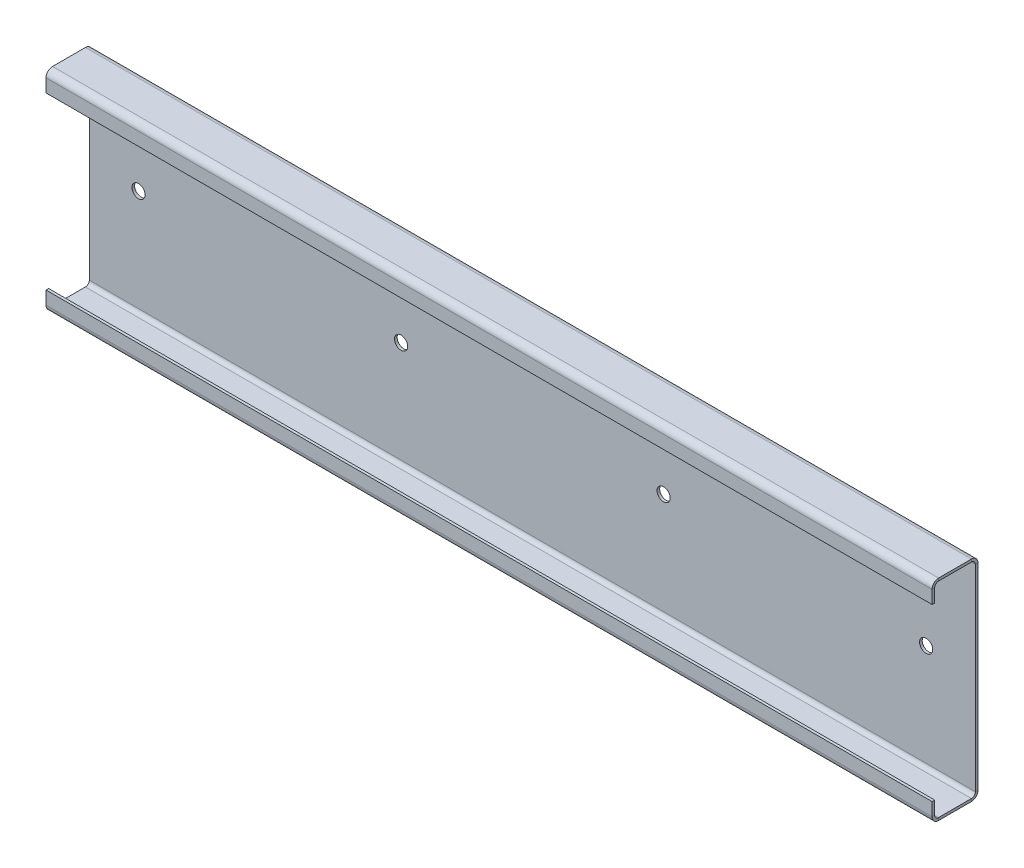
SolidWorks part; units mm, degrees
note: The reader was unsure of these and kept them because the rebuilt part matched: thickness of "Base-Flange1", "Edge-Flange1", "Edge-Flange2", "Sheet-Metal1", "Sheet-Metal2", "Sheet-Metal3", "Sheet-Metal5", "Sheet-Metal6"; flange length of "Edge-Flange1", "Edge-Flange2".
material "Galvanized Steel"
ref_plane "Front Plane" through (0, 0, 0) normal (0, 0, 1) x (1, 0, 0)
ref_plane "Top Plane" through (0, 0, 0) normal (0, 1, 0) x (1, 0, 0)
ref_plane "Right Plane" through (0, 0, 0) normal (1, 0, 0) x (0, 0, -1)
sketch "Sketch1" plane through (0, 0, 0) normal (0, 0, 1) x (1, 0, 0)
  line L1 (-337.5, -80) -> (337.5, -80)
  line L2 (-337.5, -80) -> (-337.5, 80)
  line L3 (-337.5, 80) -> (337.5, 80)
  line L4 (337.5, -80) -> (337.5, 80)
  line L5 (-337.5, -80) -> (337.5, 80) construction
  line L6 (-337.5, 80) -> (337.5, -80) construction
  point P0 (0, 0)
  dimension "D1" = 675
  dimension "D2" = 160
base flange "Base-Flange1" sketch "Sketch1" thickness 2 reverse thickness direction no parameters "D1"=3
edge flange "Edge-Flange1" sketch "Sketch10" flange profiles "Sketch10", "Sketch11" flange angle 90 flange length 35 flange position material inside bend radius 3 thickness 2 relief rectangular parameters "D6"=10, "D8"=1
sketch "Sketch10" plane through (0, 80, 0) normal (0, 1, 0) x (-1, 0, 0)
  line L0 (-337.5, 0) -> (337.5, 0) construction
  line L1 (-337.5, 0) -> (337.5, 0)
  line L2 (-337.5, 0) -> (-337.5, 33)
  line L3 (-337.5, 33) -> (337.5, 33)
  line L4 (337.5, 33) -> (337.5, 0)
sketch "Sketch11" plane through (0, -80, 0) normal (0, -1, 0) x (1, 0, 0)
  line L0 (-337.5, 0) -> (337.5, 0) construction
  line L1 (-337.5, 0) -> (337.5, 0)
  line L2 (-337.5, 0) -> (-337.5, 33)
  line L3 (-337.5, 33) -> (337.5, 33)
  line L4 (337.5, 33) -> (337.5, 0)
bend "EdgeBend1" bend radius 3 bend angle 90 parameters "D5"=1
bend "EdgeBend2" bend radius 3 bend angle 90 parameters "D5"=2
edge flange "Edge-Flange2" sketch "Sketch16" flange profiles "Sketch16", "Sketch17" flange angle 90 flange length 15 flange position material inside bend radius 3 thickness 2 relief rectangular parameters "D6"=10, "D8"=1
sketch "Sketch16" plane through (0, -78, 33) normal (0, 0, 1) x (1, 0, 0)
  line L0 (337.5, 0) -> (-337.5, 0) construction
  line L1 (337.5, 0) -> (-337.5, 0)
  line L2 (-337.5, 0) -> (-337.5, 13)
  line L3 (-337.5, 13) -> (337.5, 13)
  line L4 (337.5, 13) -> (337.5, 0)
sketch "Sketch17" plane through (0, 78, 33) normal (0, 0, 1) x (-1, 0, 0)
  line L0 (337.5, 0) -> (-337.5, 0) construction
  line L1 (337.5, 0) -> (-337.5, 0)
  line L2 (-337.5, 0) -> (-337.5, 13)
  line L3 (-337.5, 13) -> (337.5, 13)
  line L4 (337.5, 13) -> (337.5, 0)
bend "EdgeBend3" bend radius 3 bend angle 90 parameters "D5"=3
bend "EdgeBend4" bend radius 3 bend angle 90 parameters "D5"=4
sketch "Sketch18" plane through (0, 0, -2) normal (0, 0, -1) x (-1, 0, 0)
  line L0 (337.5, 80) -> (-337.5, 80) construction
  line L1 (-337.5, -75) -> (-337.5, 75) construction
  circle A0 centre (-300, 2.49) radius 5
  dimension "D1" = 10
  dimension "D2" = 77.51
  dimension "D3" = 37.5
extrude "Cut-Extrude1" cut sketch "Sketch18" against normal blind 10 normal cut yes
pattern_linear "LPattern1" count 4 spacing 200 along (-1, 0, 0) of "Cut-Extrude1"
sketch "Bend-Lines1" [suppressed] plane through (0, 0, 0) normal (0, 1, 0) x (1, 0, 0)
sketch "Bounding-Box1" [suppressed] plane through (0, 0, 0) normal (0, 1, 0) x (1, 0, 0)
sheet metal parameters "Sheet-Metal1" thickness 2 parameters "D1"=3
flat pattern "Flat-Pattern1" [suppressed]
sketch "Bend-Lines2" plane through (0, 0, 0) normal (0, 1, 0) x (1, 0, 0)
sketch3d "Bounding-Box2" [suppressed]
  line L0 (710, -80, 0) -> (-710, -80, 0) construction
  line L1 (710, 80, 0) -> (-710, 80, 0) construction
  line L2 (710, -80, 0) -> (710, 80, 0) construction
  line L3 (-710, -80, 0) -> (-710, 80, 0) construction
sheet metal parameters "Sheet-Metal2" thickness 2 parameters "D1"=3, "D7"=1.5
flat pattern "Flat-Pattern1"
sketch "Bend-Lines2" plane through (0, 0, 0) normal (0, 0, 1) x (1, 0, 0)
  line L0 (-710, -78.4452) -> (710, -78.4452) construction
  line L1 (710, 78.4452) -> (-710, 78.4452) construction
  line L2 (-710, -78.4452) -> (710, -78.4452) construction
  line L3 (710, 78.4452) -> (-710, 78.4452) construction
sketch3d "Bounding-Box2" [suppressed]
  line L0 (-710, -111.8905, 0) -> (710, -111.8905, 0) construction
  line L1 (-710, 111.8905, 0) -> (710, 111.8905, 0) construction
  line L2 (-710, -111.8905, 0) -> (-710, 111.8905, 0) construction
  line L3 (710, -111.8905, 0) -> (710, 111.8905, 0) construction
bend of the flat pattern "Flatten-<EdgeBend1>1"
bend of the flat pattern "Flatten-<EdgeBend2>1"
sheet metal parameters "Sheet-Metal3" thickness 2 parameters "D1"=3, "D7"=1.5
flat pattern "Flat-Pattern1"
sketch "Bend-Lines2" plane through (0, 0, 0) normal (0, 0, 1) x (1, 0, 0)
  line L0 (-337.5, -78.1416) -> (337.5, -78.1416) construction
  line L1 (337.5, 78.1416) -> (-337.5, 78.1416) construction
  line L2 (-337.5, -78.1416) -> (337.5, -78.1416) construction
  line L3 (337.5, 78.1416) -> (-337.5, 78.1416) construction
  line L4 (337.5, 109.4248) -> (-337.5, 109.4248) construction
  line L5 (-337.5, -109.4248) -> (337.5, -109.4248) construction
  line L6 (337.5, 109.4248) -> (-337.5, 109.4248) construction
  line L7 (-337.5, -109.4248) -> (337.5, -109.4248) construction
sketch3d "Bounding-Box2" [suppressed]
  line L0 (-337.5, -122.5664, 0) -> (337.5, -122.5664, 0) construction
  line L1 (-337.5, 122.5664, 0) -> (337.5, 122.5664, 0) construction
  line L2 (-337.5, -122.5664, 0) -> (-337.5, 122.5664, 0) construction
  line L3 (337.5, -122.5664, 0) -> (337.5, 122.5664, 0) construction
bend of the flat pattern "Flatten-<EdgeBend1>1"
bend of the flat pattern "Flatten-<EdgeBend2>1"
bend of the flat pattern "Flatten-<EdgeBend3>1"
bend of the flat pattern "Flatten-<EdgeBend4>1"
sheet metal parameters "Sheet-Metal5" thickness 2 parameters "D1"=3, "D7"=1.5
flat pattern "Flat-Pattern1"
sketch "Bend-Lines2" plane through (0, 0, 0) normal (0, 0, 1) x (1, 0, 0)
  line L0 (-337.5, -78.1416) -> (337.5, -78.1416) construction
  line L1 (337.5, 78.1416) -> (-337.5, 78.1416) construction
  line L2 (-337.5, -78.1416) -> (337.5, -78.1416) construction
  line L3 (337.5, 78.1416) -> (-337.5, 78.1416) construction
  line L4 (337.5, 109.4248) -> (-337.5, 109.4248) construction
  line L5 (-337.5, -109.4248) -> (337.5, -109.4248) construction
  line L6 (337.5, 109.4248) -> (-337.5, 109.4248) construction
  line L7 (-337.5, -109.4248) -> (337.5, -109.4248) construction
sketch3d "Bounding-Box2" [suppressed]
  line L0 (-337.5, -122.5664, 0) -> (337.5, -122.5664, 0) construction
  line L1 (-337.5, 122.5664, 0) -> (337.5, 122.5664, 0) construction
  line L2 (-337.5, -122.5664, 0) -> (-337.5, 122.5664, 0) construction
  line L3 (337.5, -122.5664, 0) -> (337.5, 122.5664, 0) construction
bend of the flat pattern "Flatten-<EdgeBend1>1"
bend of the flat pattern "Flatten-<EdgeBend2>1"
bend of the flat pattern "Flatten-<EdgeBend3>1"
bend of the flat pattern "Flatten-<EdgeBend4>1"
sheet metal parameters "Sheet-Metal6" thickness 2 parameters "D1"=3, "D7"=1.5
flat pattern "Flat-Pattern1"
sketch "Bend-Lines2" plane through (0, 0, 0) normal (0, 0, 1) x (1, 0, 0)
  line L0 (-337.5, -78.1416) -> (337.5, -78.1416) construction
  line L1 (337.5, 78.1416) -> (-337.5, 78.1416) construction
  line L2 (-337.5, -78.1416) -> (337.5, -78.1416) construction
  line L3 (337.5, 78.1416) -> (-337.5, 78.1416) construction
  line L4 (337.5, 109.4248) -> (-337.5, 109.4248) construction
  line L5 (-337.5, -109.4248) -> (337.5, -109.4248) construction
  line L6 (337.5, 109.4248) -> (-337.5, 109.4248) construction
  line L7 (-337.5, -109.4248) -> (337.5, -109.4248) construction
sketch3d "Bounding-Box2" [suppressed]
  line L0 (-337.5, -122.5664, 0) -> (337.5, -122.5664, 0) construction
  line L1 (-337.5, 122.5664, 0) -> (337.5, 122.5664, 0) construction
  line L2 (-337.5, -122.5664, 0) -> (-337.5, 122.5664, 0) construction
  line L3 (337.5, -122.5664, 0) -> (337.5, 122.5664, 0) construction
bend of the flat pattern "Flatten-<EdgeBend1>1"
bend of the flat pattern "Flatten-<EdgeBend2>1"
bend of the flat pattern "Flatten-<EdgeBend3>1"
bend of the flat pattern "Flatten-<EdgeBend4>1"
